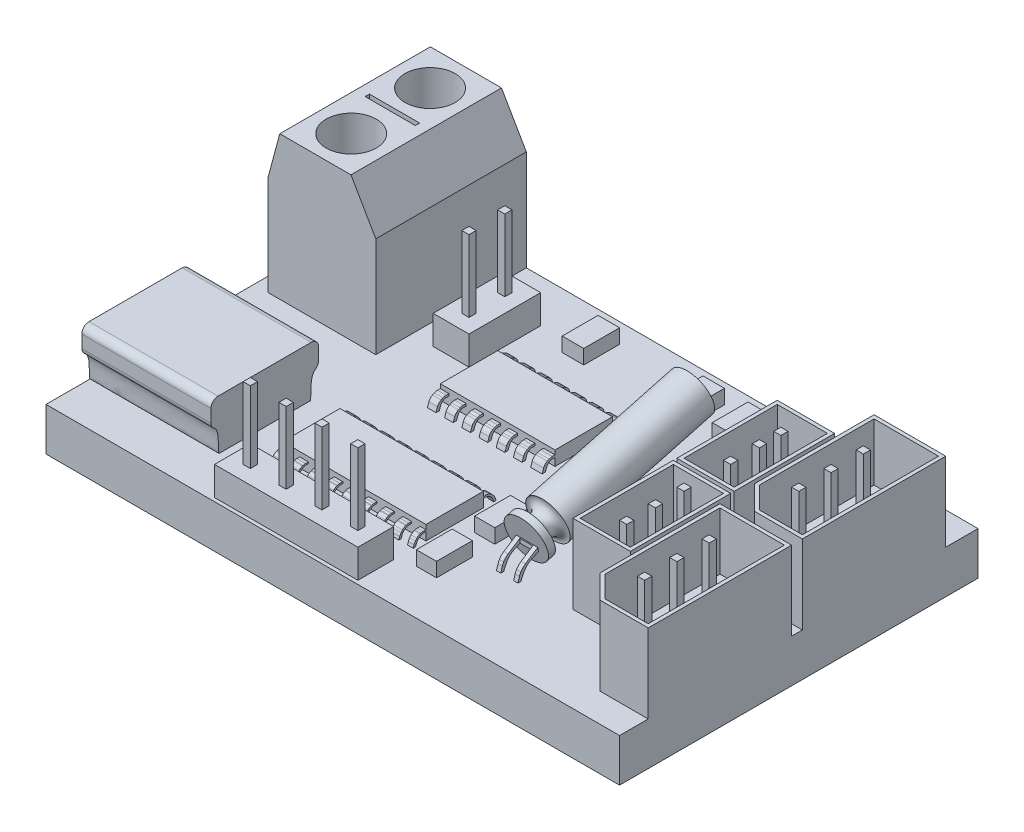
SolidWorks part; units mm, degrees
ref_plane "Front Plane" through (0, 0, 0) normal (0, 0, 1) x (1, 0, 0)
ref_plane "Top Plane" through (0, 0, 0) normal (0, 1, 0) x (1, 0, 0)
ref_plane "Right Plane" through (0, 0, 0) normal (1, 0, 0) x (0, 0, -1)
sketch "Sketch2" plane through (0, 0, 0) normal (0, 1, 0) x (1, 0, 0)
  line L1 (20, -12.5) -> (-20, -12.5)
  line L2 (20, -12.5) -> (20, 12.5)
  line L3 (20, 12.5) -> (-20, 12.5)
  line L4 (-20, -12.5) -> (-20, 12.5)
  line L5 (20, -12.5) -> (-20, 12.5) construction
  line L6 (20, 12.5) -> (-20, -12.5) construction
  point P0 (0, 0)
  dimension "D1" = 40
  dimension "D2" = 25
extrude "Boss-Extrude1" add sketch "Sketch2" against normal blind 3
sketch "Sketch3" plane through (0, 0, 0) normal (0, 1, 0) x (1, 0, 0)
  line L0 (20, 12.5) -> (-20, 12.5) construction
  line L1 (-19, 12.5) -> (-11.5, 12.5)
  line L2 (-19, 12.5) -> (-19, 2)
  line L3 (-19, 2) -> (-11.5, 2)
  line L4 (-11.5, 12.5) -> (-11.5, 2)
  line L5 (-20, 12.5) -> (-20, -12.5) construction
  dimension "D1" = 7.5
  dimension "D2" = 10.5
  dimension "D3" = 1
extrude "Boss-Extrude2" add sketch "Sketch3" along normal blind 10
sketch "Sketch4" plane through (0, 0, -2) normal (0, 0, 1) x (1, 0, 0)
  line L0 (-19, 7) -> (-18.1962, 10)
  line L1 (-19, 10) -> (-19, 0) construction
  line L2 (-19, 10) -> (-11.5, 10) construction
  line L3 (-18.1962, 10) -> (-19, 10)
  line L4 (-19, 10) -> (-19, 7)
  line L5 (-11.5, 7) -> (-13.2321, 10)
  line L6 (-11.5, 10) -> (-11.5, 0) construction
  line L7 (-13.2321, 10) -> (-11.5, 10)
  line L8 (-11.5, 10) -> (-11.5, 7)
  dimension "D1" = 3
  dimension "D2" = 3
  dimension "D3" = 15
  dimension "D4" = 30
extrude "Cut-Extrude1" cut sketch "Sketch4" against normal up to surface (10.5 mm away) up to face at (-7.625, 1.75, -12.5)
sketch "Sketch5" plane through (0, 10, 0) normal (0, 1, 0) x (1, 0, 0)
  line L0 (-13.2321, 12.5) -> (-18.1962, 12.5) construction
  line L1 (-17.4641, 7.522) -> (-13.9641, 7.522)
  line L2 (-17.4641, 7.522) -> (-17.4641, 7.222)
  line L3 (-17.4641, 7.222) -> (-13.9641, 7.222)
  line L4 (-13.9641, 7.522) -> (-13.9641, 7.222)
  line L5 (-19, 2) -> (-11.5, 2) construction
  circle A0 centre (-15.7141, 10) radius 1.75
  circle A1 centre (-15.7141, 4.5) radius 1.75
  point P10 (-15.7141, 12.5)
  point P11 (-15.7141, 7.522)
  dimension "D3" = 3.5
  dimension "D4" = 3.5
  dimension "D1" = 0.3
  dimension "D2" = 3.5
  dimension "D5" = 2.5
  dimension "D6" = 2.5
extrude "Cut-Extrude2" cut sketch "Sketch5" against normal blind 5
sketch "Sketch6" plane through (-19, 0, 0) normal (-1, 0, 0) x (0, 0, 1)
  line L0 (-2, 7) -> (-2, 0) construction
  line L1 (-12, 5.5) -> (-7.5, 5.5)
  line L2 (-12, 5.5) -> (-12, 1)
  line L3 (-12, 1) -> (-7.5, 1)
  line L4 (-7.5, 5.5) -> (-7.5, 1)
  line L5 (-12, 5.5) -> (-7.5, 1) construction
  line L6 (-12, 1) -> (-7.5, 5.5) construction
  line L7 (-7, 5.5) -> (-2.5, 5.5)
  line L8 (-7, 5.5) -> (-7, 1)
  line L9 (-7, 1) -> (-2.5, 1)
  line L10 (-2.5, 5.5) -> (-2.5, 1)
  line L11 (-7, 5.5) -> (-2.5, 1) construction
  line L12 (-7, 1) -> (-2.5, 5.5) construction
  line L13 (-12.5, 7) -> (-12.5, 0) construction
  line L14 (-12.5, 0) -> (-2, 0) construction
  point P0 (-9.75, 3.25)
  point P5 (-4.75, 3.25)
  point P10 (-10.0583, 3.2972)
  point P11 (-4.8741, 3.5631)
  point P12 (-10.0064, 3.0499)
  point P13 (-4.7649, 3.0499)
  point P14 (0, 0)
  point P15 (-10.1096, 3.1427)
  dimension "D1" = 4.5
  dimension "D2" = 4.5
  dimension "D3" = 4.5
  dimension "D4" = 4.5
  dimension "D5" = 0.5
  dimension "D6" = 0.5
  dimension "D7" = 1
extrude "Cut-Extrude3" cut sketch "Sketch6" against normal blind 5
sketch "Sketch7" plane through (0, 0, 0) normal (0, 1, 0) x (1, 0, 0)
  line L0 (-20, 12.5) -> (-20, -12.5) construction
  line L1 (-11, -10) -> (-20, -10)
  line L2 (-11, -10) -> (-11, -2.5)
  line L3 (-11, -2.5) -> (-20, -2.5)
  line L4 (-20, -10) -> (-20, -2.5)
  line L5 (-11, -10) -> (-20, -2.5) construction
  line L6 (-11, -2.5) -> (-20, -10) construction
  line L7 (-20, -12.5) -> (20, -12.5) construction
  point P0 (-15.5, -6.25)
  dimension "D1" = 7.5
  dimension "D2" = 9
  dimension "D3" = 2.5
extrude "Boss-Extrude3" add sketch "Sketch7" along normal blind 3.5
sketch "Sketch8" plane through (-20, 0, 0) normal (-1, 0, 0) x (0, 0, 1)
  line L0 (6.25, 5.2143) -> (6.25, -0.441) construction
  line L1 (2.5, 3.5) -> (10, 3.5) construction
  line L2 (2.5, 3.5) -> (2.5, 0) construction
  line L3 (2.5, 0) -> (3.1127, 0)
  line L4 (2.5, 1.75) -> (2.5, 0)
  line L5 (10, 1.75) -> (10, 0)
  line L6 (10, 0) -> (9.3873, 0)
  spline S0 degree 3 poles (2.5, 1.75) (3.2855, 1.8357) (2.8866, -0.1418) (3.1127, 0) knots 0 0 0 0 1 1 1 1
  spline S1 degree 3 poles (10, 1.75) (9.2145, 1.8357) (9.6134, -0.1418) (9.3873, 0) knots 0 0 0 0 1 1 1 1
  point P4 (6.25, 3.5)
  line M15 (10, 0) -> (10, 3.5)
  line M17 (2.5, 3.5) -> (2.5, 0)
extrude "Cut-Extrude4" cut sketch "Sketch8" against normal blind 13.5 contours S0 L3 M17 | S1 L6 M15 region at (-20, 0.8013, 2.7456) region at (-20, 0.8013, 9.7544)
fillet "Fillet1" radius 0.5 4 edges at (-15.5, 1.75, 10) (-15.5, 1.75, 2.5) (-15.5, 3.5, 2.5) (-15.5, 3.5, 10)
sketch "Sketch9" plane through (-20, 0, 0) normal (-1, 0, 0) x (0, 0, 1)
  line L0 (3.25, 0.25) -> (9.25, 0.25)
  line L1 (6.25, 3.8986) -> (6.25, 0.8013) construction
  line L2 (3, 3.5) -> (9.5, 3.5) construction
  line L3 (9.4263, 0) -> (12.5, 0) construction
  line L4 (9.4639, 3.25) -> (3.0361, 3.25)
  spline S0 degree 3 poles (9.25, 0.25) (9.2002, 0.8034) (9.2979, 1.1822) (9.4331, 1.8514) (9.7825, 1.9035) (9.8466, 2.3039) (9.7756, 2.7644) (9.8573, 3.2635) (9.4639, 3.25) knots 0 0 0 0 0.398944 0.460389 0.554943 0.650182 0.770421 1 1 1 1
  spline S1 degree 3 poles (3.25, 0.25) (3.2998, 0.8034) (3.2021, 1.1822) (3.0669, 1.8514) (2.7175, 1.9035) (2.6534, 2.3039) (2.7244, 2.7644) (2.6427, 3.2635) (3.0361, 3.25) knots 0 0 0 0 0.398944 0.460389 0.554943 0.650182 0.770421 1 1 1 1
  point P6 (6.25, 3.5)
  point P14 (6.25, 0.25)
  point P27 (6.25, 3.25)
  dimension "D1" = 3
  dimension "D2" = 0.25
  dimension "D3" = 0.25
extrude "Cut-Extrude5" cut sketch "Sketch9" against normal blind 8.5
sketch "Sketch10" plane through (0, 0, 0) normal (0, 1, 0) x (1, 0, 0)
  line L0 (-11.5, 2) -> (-11.5, 12.5) construction
  line L1 (-10, 9.5) -> (-7.5, 9.5)
  line L2 (-10, 9.5) -> (-10, 4.5)
  line L3 (-10, 4.5) -> (-7.5, 4.5)
  line L4 (-7.5, 9.5) -> (-7.5, 4.5)
  line L5 (-10, 9.5) -> (-7.5, 4.5) construction
  line L6 (-10, 4.5) -> (-7.5, 9.5) construction
  line L7 (20, 12.5) -> (-11.5, 12.5) construction
  point P0 (-8.75, 7)
  point P5 (-8.5445, 7.4217)
  dimension "D1" = 5
  dimension "D2" = 2.5
  dimension "D3" = 1.5
  dimension "D4" = 3
extrude "Boss-Extrude4" add sketch "Sketch10" along normal blind 2
sketch "Sketch11" plane through (0, 2, 0) normal (0, 1, 0) x (1, 0, 0)
  line L0 (-7.5, 9.5) -> (-10, 9.5) construction
  line L1 (-8.5, 8) -> (-9, 8)
  line L2 (-8.5, 8) -> (-8.5, 8.5)
  line L3 (-8.5, 8.5) -> (-9, 8.5)
  line L4 (-9, 8) -> (-9, 8.5)
  line L5 (-8.5, 8) -> (-9, 8.5) construction
  line L6 (-8.5, 8.5) -> (-9, 8) construction
  line L7 (-8.5027, 5.5) -> (-9.0027, 5.5)
  line L8 (-8.5027, 5.5) -> (-8.5027, 6)
  line L9 (-8.5027, 6) -> (-9.0027, 6)
  line L10 (-9.0027, 5.5) -> (-9.0027, 6)
  line L11 (-8.5027, 5.5) -> (-9.0027, 6) construction
  line L12 (-8.5027, 6) -> (-9.0027, 5.5) construction
  line L13 (-7.5, 4.5) -> (-7.5, 9.5) construction
  line L14 (-10, 4.5) -> (-7.5, 4.5) construction
  point P0 (-8.75, 8.25)
  point P5 (-8.7527, 5.75)
  dimension "D1" = 0.5
  dimension "D2" = 0.5
  dimension "D3" = 0.5
  dimension "D4" = 0.5
  dimension "D5" = 1.25
  dimension "D6" = 1.25
  dimension "D7" = 1.2527
  dimension "D8" = 1.25
extrude "Boss-Extrude5" add sketch "Sketch11" along normal blind 5
sketch "Sketch12" plane through (0, 0, 0) normal (0, 1, 0) x (1, 0, 0)
  line L0 (-11, -9.5) -> (-11, -3) construction
  line L1 (-8.5, -9.75) -> (1.5, -9.75)
  line L2 (-8.5, -9.75) -> (-8.5, -12.25)
  line L3 (-8.5, -12.25) -> (1.5, -12.25)
  line L4 (1.5, -9.75) -> (1.5, -12.25)
  line L5 (-20, -12.5) -> (20, -12.5) construction
  dimension "D1" = 2.5
  dimension "D2" = 10
  dimension "D3" = 2.5
  dimension "D4" = 0.25
extrude "Boss-Extrude6" add sketch "Sketch12" along normal blind 2
sketch "Sketch13" plane through (0, 2, 0) normal (0, 1, 0) x (1, 0, 0)
  line L0 (-8.5, -9.75) -> (-8.5, -12.25) construction
  line L1 (-7, -11.25) -> (-7.5, -11.25)
  line L2 (-7, -11.25) -> (-7, -10.75)
  line L3 (-7, -10.75) -> (-7.5, -10.75)
  line L4 (-7.5, -11.25) -> (-7.5, -10.75)
  line L5 (-7, -11.25) -> (-7.5, -10.75) construction
  line L6 (-7, -10.75) -> (-7.5, -11.25) construction
  line L8 (1.5, -9.75) -> (-8.5, -9.75) construction
  line L9 (-5, -11.25) -> (-5, -10.75)
  line L10 (-4.5, -10.75) -> (-5, -10.75)
  line L11 (-4.5, -11.25) -> (-4.5, -10.75)
  line L12 (-4.5, -11.25) -> (-5, -11.25)
  line L13 (-2.5, -11.25) -> (-2.5, -10.75)
  line L14 (-2, -10.75) -> (-2.5, -10.75)
  line L15 (-2, -11.25) -> (-2, -10.75)
  line L16 (-2, -11.25) -> (-2.5, -11.25)
  line L17 (0, -11.25) -> (0, -10.75)
  line L18 (0.5, -10.75) -> (0, -10.75)
  line L19 (0.5, -11.25) -> (0.5, -10.75)
  line L20 (0.5, -11.25) -> (0, -11.25)
  point P0 (-7.25, -11)
  dimension "D1" = 1.25
  dimension "D2" = 1.25
  dimension "D3" = 0.5
  dimension "D4" = 0.5
  dimension "D5" = 4
extrude "Boss-Extrude7" add sketch "Sketch13" along normal blind 5
sketch "Sketch14" plane through (0, 0, 0) normal (0, 1, 0) x (1, 0, 0)
  line L0 (-7.5, 4.5) -> (-7.5, 9.5) construction
  line L1 (-6.5, 5.5) -> (1.5, 5.5)
  line L2 (-6.5, 5.5) -> (-6.5, 1.5)
  line L3 (-6.5, 1.5) -> (1.5, 1.5)
  line L4 (1.5, 5.5) -> (1.5, 1.5)
  line L5 (-8.5, -3.5) -> (1.5, -3.5)
  line L6 (-8.5, -3.5) -> (-8.5, -7.5)
  line L7 (-8.5, -7.5) -> (1.5, -7.5)
  line L8 (1.5, -3.5) -> (1.5, -7.5)
  line L9 (20, 12.5) -> (-11.5, 12.5) construction
  dimension "D1" = 8
  dimension "D2" = 4
  dimension "D3" = 4
  dimension "D4" = 10
  dimension "D5" = 1
  dimension "D6" = 7
  dimension "D7" = 5
extrude "Boss-Extrude8" add sketch "Sketch14" along normal blind 1
sketch "Sketch15" plane through (1.5, 0, 0) normal (1, 0, 0) x (0, 0, -1)
  line L0 (1.5, 0.7025) -> (1.3027, 0.7025)
  line L1 (1.5, 1) -> (1.5, 0) construction
  line L2 (1.0838, 0.6521) -> (0.9577, 0.5907)
  line L3 (0.704, 0.3042) -> (0.599, 0)
  line L4 (-12.5, 0) -> (12.5, 0) construction
  line L5 (0.599, 0) -> (0.8295, 0)
  line L6 (0.8295, 0) -> (0.9119, 0.2391)
  line L7 (1.1657, 0.5256) -> (1.216, 0.5501)
  line L8 (1.216, 0.5501) -> (1.5, 0.5501)
  line L9 (3.5, 2.4985) -> (3.5, 0.0788) construction
  line L10 (1.5, 1) -> (5.5, 1) construction
  line L11 (1.5, 0.7025) -> (1.5, 0.5501)
  line L12 (5.5, 0.7025) -> (5.5, 0.5501)
  line L13 (5.784, 0.5501) -> (5.5, 0.5501)
  line L14 (5.8343, 0.5256) -> (5.784, 0.5501)
  line L15 (6.1705, 0) -> (6.0881, 0.2391)
  line L16 (6.401, 0) -> (6.1705, 0)
  line L17 (6.296, 0.3042) -> (6.401, 0)
  line L18 (5.9162, 0.6521) -> (6.0423, 0.5907)
  line L19 (5.5, 0.7025) -> (5.6973, 0.7025)
  arc A0 (1.3027, 0.7025) -> (1.0838, 0.6521) centre (1.3027, 0.2025) ccw
  arc A1 (0.9119, 0.2391) -> (1.1657, 0.5256) centre (1.3846, 0.076) cw
  arc A2 (0.704, 0.3042) -> (0.9577, 0.5907) centre (1.1767, 0.1412) cw
  arc A3 (6.296, 0.3042) -> (6.0423, 0.5907) centre (5.8233, 0.1412) ccw
  arc A4 (6.0881, 0.2391) -> (5.8343, 0.5256) centre (5.6154, 0.076) ccw
  arc A5 (5.6973, 0.7025) -> (5.9162, 0.6521) centre (5.6973, 0.2025) cw
  point P16 (3.5, 1)
  dimension "D1" = 0.5
extrude "Boss-Extrude9" add sketch "Sketch15" against normal up to surface (8 mm away) up to face at (-6.5, 0.5, -3.5)
sketch "Sketch16" plane through (1.5, 0, 0) normal (1, 0, 0) x (0, 0, -1)
  line L0 (-7.5, 0.6782) -> (-7.7045, 0.6782)
  line L1 (-7.5, 1) -> (-7.5, 0) construction
  line L2 (-7.8691, 0.6503) -> (-7.9154, 0.6342)
  line L3 (-8.1339, 0.4833) -> (-8.2332, 0.3648)
  line L4 (-8.3282, 0.1901) -> (-8.3864, 0)
  line L5 (-12.5, 0) -> (12.5, 0) construction
  line L6 (-8.3864, 0) -> (-8.2252, 0)
  line L7 (-8.2252, 0) -> (-8.1768, 0.1579)
  line L8 (-8.0819, 0.3327) -> (-8.0568, 0.3626)
  line L9 (-7.9199, 0.4766) -> (-7.8668, 0.5066)
  line L10 (-7.6206, 0.5714) -> (-7.5, 0.5714)
  line L11 (-7.5, 0.6782) -> (-7.5, 0.5714)
  line L12 (-5.5, 2.2485) -> (-5.5, -1.2373) construction
  line L13 (-7.5, 1) -> (-3.5, 1) construction
  line L14 (-3.5, 0.6782) -> (-3.5, 0.5714)
  line L15 (-3.3794, 0.5714) -> (-3.5, 0.5714)
  line L16 (-3.0801, 0.4766) -> (-3.1332, 0.5066)
  line L17 (-2.9181, 0.3327) -> (-2.9432, 0.3626)
  line L18 (-2.7748, 0) -> (-2.8232, 0.1579)
  line L19 (-2.6136, 0) -> (-2.7748, 0)
  line L20 (-2.6718, 0.1901) -> (-2.6136, 0)
  line L21 (-2.8661, 0.4833) -> (-2.7668, 0.3648)
  line L22 (-3.1309, 0.6503) -> (-3.0846, 0.6342)
  line L23 (-3.5, 0.6782) -> (-3.2955, 0.6782)
  arc A1 (-7.7045, 0.6782) -> (-7.8691, 0.6503) centre (-7.7045, 0.1782) ccw
  arc A2 (-7.8668, 0.5066) -> (-7.6206, 0.5714) centre (-7.6206, 0.0714) cw
  arc A3 (-8.0568, 0.3626) -> (-7.9199, 0.4766) centre (-7.6737, 0.0414) cw
  arc A4 (-8.1768, 0.1579) -> (-8.0819, 0.3327) centre (-7.6987, 0.0115) cw
  arc A5 (-8.2332, 0.3648) -> (-8.3282, 0.1901) centre (-7.8501, 0.0436) ccw
  arc A6 (-7.9154, 0.6342) -> (-8.1339, 0.4833) centre (-7.7508, 0.1621) ccw
  arc A7 (-3.0846, 0.6342) -> (-2.8661, 0.4833) centre (-3.2492, 0.1621) cw
  arc A8 (-2.7668, 0.3648) -> (-2.6718, 0.1901) centre (-3.1499, 0.0436) cw
  arc A9 (-2.8232, 0.1579) -> (-2.9181, 0.3327) centre (-3.3013, 0.0115) ccw
  arc A10 (-2.9432, 0.3626) -> (-3.0801, 0.4766) centre (-3.3263, 0.0414) ccw
  arc A11 (-3.1332, 0.5066) -> (-3.3794, 0.5714) centre (-3.3794, 0.0714) ccw
  arc A12 (-3.2955, 0.6782) -> (-3.1309, 0.6503) centre (-3.2955, 0.1782) cw
  point P16 (-5.5, 1)
  dimension "D1" = 0.5
extrude "Boss-Extrude10" add sketch "Sketch16" against normal up to surface (10 mm away) up to face at (-8.5, 0.5, 5.5)
sketch "Sketch17" plane through (0, 0, 0) normal (0, 1, 0) x (1, 0, 0)
  line L0 (-6.5, 6.401) -> (1.5, 6.401) construction
  line L1 (-5.9, 6.401) -> (-5.3, 6.401)
  line L2 (-5.9, 6.401) -> (-5.9, 5.5)
  line L3 (-5.9, 5.5) -> (-5.3, 5.5)
  line L4 (-5.3, 6.401) -> (-5.3, 5.5)
  line L5 (-6.5, 5.5) -> (1.5, 5.5) construction
  line L6 (-6.5, 1.5) -> (1.5, 1.5) construction
  line L7 (-5.9, 1.5) -> (-5.3, 1.5)
  line L8 (-5.9, 1.5) -> (-5.9, 0.599)
  line L9 (-5.9, 0.599) -> (-5.3, 0.599)
  line L10 (-5.3, 1.5) -> (-5.3, 0.599)
  line L11 (-6.5, 0.599) -> (1.5, 0.599) construction
  line L12 (-6.5, 6.296) -> (-6.5, 6.0423) construction
  line L13 (-4.1, 1.5) -> (-4.1, 0.599)
  line L14 (-4.7, 1.5) -> (-4.1, 1.5)
  line L15 (-4.7, 1.5) -> (-4.7, 0.599)
  line L16 (-4.7, 0.599) -> (-4.1, 0.599)
  line L17 (-4.7, 5.5) -> (-4.1, 5.5)
  line L18 (-4.7, 6.401) -> (-4.7, 5.5)
  line L19 (-4.1, 6.401) -> (-4.1, 5.5)
  line L20 (-4.7, 6.401) -> (-4.1, 6.401)
  line L21 (-2.9, 1.5) -> (-2.9, 0.599)
  line L22 (-3.5, 1.5) -> (-2.9, 1.5)
  line L23 (-3.5, 1.5) -> (-3.5, 0.599)
  line L24 (-3.5, 0.599) -> (-2.9, 0.599)
  line L25 (-3.5, 5.5) -> (-2.9, 5.5)
  line L26 (-3.5, 6.401) -> (-3.5, 5.5)
  line L27 (-2.9, 6.401) -> (-2.9, 5.5)
  line L28 (-3.5, 6.401) -> (-2.9, 6.401)
  line L29 (-1.7, 1.5) -> (-1.7, 0.599)
  line L30 (-2.3, 1.5) -> (-1.7, 1.5)
  line L31 (-2.3, 1.5) -> (-2.3, 0.599)
  line L32 (-2.3, 0.599) -> (-1.7, 0.599)
  line L33 (-2.3, 5.5) -> (-1.7, 5.5)
  line L34 (-2.3, 6.401) -> (-2.3, 5.5)
  line L35 (-1.7, 6.401) -> (-1.7, 5.5)
  line L36 (-2.3, 6.401) -> (-1.7, 6.401)
  line L37 (-0.5, 1.5) -> (-0.5, 0.599)
  line L38 (-1.1, 1.5) -> (-0.5, 1.5)
  line L39 (-1.1, 1.5) -> (-1.1, 0.599)
  line L40 (-1.1, 0.599) -> (-0.5, 0.599)
  line L41 (-1.1, 5.5) -> (-0.5, 5.5)
  line L42 (-1.1, 6.401) -> (-1.1, 5.5)
  line L43 (-0.5, 6.401) -> (-0.5, 5.5)
  line L44 (-1.1, 6.401) -> (-0.5, 6.401)
  line L45 (0.7, 1.5) -> (0.7, 0.599)
  line L46 (0.1, 1.5) -> (0.7, 1.5)
  line L47 (0.1, 1.5) -> (0.1, 0.599)
  line L48 (0.1, 0.599) -> (0.7, 0.599)
  line L49 (0.1, 5.5) -> (0.7, 5.5)
  line L50 (0.1, 6.401) -> (0.1, 5.5)
  line L51 (0.7, 6.401) -> (0.7, 5.5)
  line L52 (0.1, 6.401) -> (0.7, 6.401)
  line L53 (-8.5, -2.6136) -> (1.5, -2.6136) construction
  line L54 (-7.9, -2.6136) -> (-7.3, -2.6136)
  line L55 (-7.9, -2.6136) -> (-7.9, -3.5)
  line L56 (-7.9, -3.5) -> (-7.3, -3.5)
  line L57 (-7.3, -2.6136) -> (-7.3, -3.5)
  line L58 (1.5, -3.5) -> (-8.5, -3.5) construction
  line L59 (-8.5, -7.5) -> (1.5, -7.5) construction
  line L60 (-7.9, -7.5) -> (-7.3, -7.5)
  line L61 (-7.9, -7.5) -> (-7.9, -8.3864)
  line L62 (-7.9, -8.3864) -> (-7.3, -8.3864)
  line L63 (-7.3, -7.5) -> (-7.3, -8.3864)
  line L64 (-8.5, -8.3864) -> (1.5, -8.3864) construction
  line L65 (-8.5, -2.8661) -> (-8.5, -3.0846) construction
  line L66 (-8.5, -7.7045) -> (-8.5, -7.8691) construction
  line L67 (-6.7, -2.6136) -> (-6.7, -3.5)
  line L68 (-6.7, -2.6136) -> (-6.1, -2.6136)
  line L69 (-6.1, -2.6136) -> (-6.1, -3.5)
  line L70 (-6.7, -3.5) -> (-6.1, -3.5)
  line L71 (-6.7, -7.5) -> (-6.7, -8.3864)
  line L72 (-6.7, -7.5) -> (-6.1, -7.5)
  line L73 (-6.1, -7.5) -> (-6.1, -8.3864)
  line L74 (-6.7, -8.3864) -> (-6.1, -8.3864)
  line L75 (-5.5, -2.6136) -> (-5.5, -3.5)
  line L76 (-5.5, -2.6136) -> (-4.9, -2.6136)
  line L77 (-4.9, -2.6136) -> (-4.9, -3.5)
  line L78 (-5.5, -3.5) -> (-4.9, -3.5)
  line L79 (-5.5, -7.5) -> (-5.5, -8.3864)
  line L80 (-5.5, -7.5) -> (-4.9, -7.5)
  line L81 (-4.9, -7.5) -> (-4.9, -8.3864)
  line L82 (-5.5, -8.3864) -> (-4.9, -8.3864)
  line L83 (-4.3, -2.6136) -> (-4.3, -3.5)
  line L84 (-4.3, -2.6136) -> (-3.7, -2.6136)
  line L85 (-3.7, -2.6136) -> (-3.7, -3.5)
  line L86 (-4.3, -3.5) -> (-3.7, -3.5)
  line L87 (-4.3, -7.5) -> (-4.3, -8.3864)
  line L88 (-4.3, -7.5) -> (-3.7, -7.5)
  line L89 (-3.7, -7.5) -> (-3.7, -8.3864)
  line L90 (-4.3, -8.3864) -> (-3.7, -8.3864)
  line L91 (-3.1, -2.6136) -> (-3.1, -3.5)
  line L92 (-3.1, -2.6136) -> (-2.5, -2.6136)
  line L93 (-2.5, -2.6136) -> (-2.5, -3.5)
  line L94 (-3.1, -3.5) -> (-2.5, -3.5)
  line L95 (-3.1, -7.5) -> (-3.1, -8.3864)
  line L96 (-3.1, -7.5) -> (-2.5, -7.5)
  line L97 (-2.5, -7.5) -> (-2.5, -8.3864)
  line L98 (-3.1, -8.3864) -> (-2.5, -8.3864)
  line L99 (-1.9, -2.6136) -> (-1.9, -3.5)
  line L100 (-1.9, -2.6136) -> (-1.3, -2.6136)
  line L101 (-1.3, -2.6136) -> (-1.3, -3.5)
  line L102 (-1.9, -3.5) -> (-1.3, -3.5)
  line L103 (-1.9, -7.5) -> (-1.9, -8.3864)
  line L104 (-1.9, -7.5) -> (-1.3, -7.5)
  line L105 (-1.3, -7.5) -> (-1.3, -8.3864)
  line L106 (-1.9, -8.3864) -> (-1.3, -8.3864)
  line L107 (-0.7, -2.6136) -> (-0.7, -3.5)
  line L108 (-0.7, -2.6136) -> (-0.1, -2.6136)
  line L109 (-0.1, -2.6136) -> (-0.1, -3.5)
  line L110 (-0.7, -3.5) -> (-0.1, -3.5)
  line L111 (-0.7, -7.5) -> (-0.7, -8.3864)
  line L112 (-0.7, -7.5) -> (-0.1, -7.5)
  line L113 (-0.1, -7.5) -> (-0.1, -8.3864)
  line L114 (-0.7, -8.3864) -> (-0.1, -8.3864)
  line L115 (0.5, -2.6136) -> (0.5, -3.5)
  line L116 (0.5, -2.6136) -> (1.1, -2.6136)
  line L117 (1.1, -2.6136) -> (1.1, -3.5)
  line L118 (0.5, -3.5) -> (1.1, -3.5)
  line L119 (0.5, -7.5) -> (0.5, -8.3864)
  line L120 (0.5, -7.5) -> (1.1, -7.5)
  line L121 (1.1, -7.5) -> (1.1, -8.3864)
  line L122 (0.5, -8.3864) -> (1.1, -8.3864)
  dimension "D1" = 0.6
  dimension "D2" = 0.6
  dimension "D3" = 0.6
  dimension "D5" = 0.6
  dimension "D6" = 0.6
  dimension "D7" = 0.6
  dimension "D8" = 0.6
  dimension "D4" = 6
  dimension "D9" = 8
extrude "Cut-Extrude6" cut sketch "Sketch17" along normal blind 1
sketch "Sketch18" plane through (0, 0, 0) normal (0, 1, 0) x (1, 0, 0)
  line L0 (15.25, 10) -> (19.75, 10)
  line L1 (19.75, 10) -> (19.75, 0.5)
  line L2 (19.75, 0.5) -> (16.75, 0.5)
  line L5 (16.75, 0.5) -> (15.25, 2)
  line L6 (15.25, 2) -> (15.25, 10)
  line L7 (20, -12.5) -> (20, 12.5) construction
  line L8 (20, 12.5) -> (-11.5, 12.5) construction
  line L9 (15.25, -0.75) -> (19.75, -0.75)
  line L10 (19.75, -0.75) -> (19.75, -10.25)
  line L11 (19.75, -10.25) -> (16.75, -10.25)
  line L12 (16.75, -10.25) -> (15.25, -8.75)
  line L13 (15.25, -8.75) -> (15.25, -0.75)
  line L14 (-20, -12.5) -> (20, -12.5) construction
  line L21 (11, 7.5) -> (14.5, 7.5)
  line L22 (11, 7.5) -> (11, 1)
  line L23 (11, 1) -> (14.5, 1)
  line L24 (14.5, 7.5) -> (14.5, 1)
  line L25 (11, 0.25) -> (14.5, 0.25)
  line L26 (11, 0.25) -> (11, -6.25)
  line L27 (11, -6.25) -> (14.5, -6.25)
  line L28 (14.5, 0.25) -> (14.5, -6.25)
  dimension "D1" = 9.5
  dimension "D2" = 4.5
  dimension "D3" = 135
  dimension "D4" = 0.25
  dimension "D5" = 2.5
  dimension "D6" = 3
  dimension "D7" = 135
  dimension "D8" = 3
  dimension "D9" = 9.5
  dimension "D10" = 4.5
  dimension "D11" = 0.25
  dimension "D12" = 2.25
  dimension "D13" = 3.5
  dimension "D14" = 3.5
  dimension "D15" = 6.5
  dimension "D16" = 6.5
  dimension "D17" = 0.75
  dimension "D18" = 0.75
  dimension "D19" = 2.5
  dimension "D20" = 0.75
extrude "Extrude-Thin1" add sketch "Sketch18" along normal blind 5.5 thin thin type one direction wall 0.25
sketch "Sketch19" plane through (0, 0, 0) normal (0, 1, 0) x (1, 0, 0)
  line L0 (19.75, 0.5) -> (19.75, 10) construction
  line L1 (11, 7.5) -> (14.5, 7.5)
  line L2 (11, 7.5) -> (11, 1)
  line L3 (11, 1) -> (14.5, 1)
  line L4 (14.5, 7.5) -> (14.5, 1)
  line L5 (11, 0.25) -> (14.5, 0.25)
  line L6 (11, 0.25) -> (11, -6.25)
  line L7 (11, -6.25) -> (14.5, -6.25)
  line L8 (14.5, 0.25) -> (14.5, -6.25)
  line L9 (19.75, 10) -> (15.25, 10) construction
  line L10 (15.25, 10) -> (15.25, 2) construction
  line L11 (15.25, 2) -> (16.75, 0.5) construction
  line L12 (16.75, 0.5) -> (19.75, 0.5) construction
  line L13 (19.75, -10.25) -> (19.75, -0.75) construction
  line L14 (19.75, -0.75) -> (15.25, -0.75) construction
  line L15 (15.25, -0.75) -> (15.25, -8.75) construction
  line L16 (15.25, -8.75) -> (16.75, -10.25) construction
  line L17 (16.75, -10.25) -> (19.75, -10.25) construction
  line L18 (19.75, 0.5) -> (19.75, 10)
  line L19 (19.75, 10) -> (15.25, 10)
  line L20 (15.25, 10) -> (15.25, 2)
  line L21 (15.25, 2) -> (16.75, 0.5)
  line L22 (16.75, 0.5) -> (19.75, 0.5)
  line L23 (19.75, -10.25) -> (19.75, -0.75)
  line L24 (19.75, -0.75) -> (15.25, -0.75)
  line L25 (15.25, -0.75) -> (15.25, -8.75)
  line L26 (15.25, -8.75) -> (16.75, -10.25)
  line L27 (16.75, -10.25) -> (19.75, -10.25)
extrude "Boss-Extrude11" add sketch "Sketch19" along normal blind 1.5
sketch "Sketch20" plane through (0, 1.5, 0) normal (0, 1, 0) x (1, 0, 0)
  line L0 (16.5, 5.25) -> (17, 5.25)
  line L1 (16.5, 8) -> (17, 8)
  line L2 (16.5, 8) -> (16.5, 7.5)
  line L3 (16.5, 7.5) -> (17, 7.5)
  line L4 (17, 8) -> (17, 7.5)
  line L5 (16.5, 5.25) -> (16.5, 5.75)
  line L6 (16.5, 5.75) -> (17, 5.75)
  line L7 (17, 5.25) -> (17, 5.75)
  line L8 (16.5, 3.5) -> (17, 3.5)
  line L9 (16.5, 3.5) -> (16.5, 3)
  line L10 (16.5, 3) -> (17, 3)
  line L11 (17, 3.5) -> (17, 3)
  line L12 (16.5, -2.75) -> (17, -2.75)
  line L13 (16.5, -2.75) -> (16.5, -3.25)
  line L14 (16.5, -3.25) -> (17, -3.25)
  line L15 (17, -2.75) -> (17, -3.25)
  line L16 (16.5, -5) -> (17, -5)
  line L17 (16.5, -5) -> (16.5, -5.5)
  line L18 (16.5, -5.5) -> (17, -5.5)
  line L19 (17, -5) -> (17, -5.5)
  line L20 (16.5, -7.25) -> (17, -7.25)
  line L21 (16.5, -7.25) -> (16.5, -7.75)
  line L22 (16.5, -7.75) -> (17, -7.75)
  line L23 (17, -7.25) -> (17, -7.75)
  line L24 (12.5, -0.5) -> (13, -0.5)
  line L25 (12.5, -0.5) -> (12.5, -1)
  line L26 (12.5, -1) -> (13, -1)
  line L27 (13, -0.5) -> (13, -1)
  line L28 (12.5, -2.5) -> (13, -2.5)
  line L29 (12.5, -2.5) -> (12.5, -3)
  line L30 (12.5, -3) -> (13, -3)
  line L31 (13, -2.5) -> (13, -3)
  line L32 (12.5, -4.5) -> (13, -4.5)
  line L33 (12.5, -4.5) -> (12.5, -5)
  line L34 (12.5, -5) -> (13, -5)
  line L35 (13, -4.5) -> (13, -5)
  line L36 (12.5, 2.75) -> (13, 2.75)
  line L37 (12.5, 2.75) -> (12.5, 2.25)
  line L38 (12.5, 2.25) -> (13, 2.25)
  line L39 (13, 2.75) -> (13, 2.25)
  line L40 (12.5, 4.75) -> (13, 4.75)
  line L41 (12.5, 4.75) -> (12.5, 4.25)
  line L42 (12.5, 4.25) -> (13, 4.25)
  line L43 (13, 4.75) -> (13, 4.25)
  line L44 (12.5, 5.75) -> (13, 5.75)
  line L45 (12.5, 5.75) -> (12.5, 6.25)
  line L46 (12.5, 6.25) -> (13, 6.25)
  line L47 (13, 5.75) -> (13, 6.25)
  line L48 (11, 1) -> (14.5, 1) construction
  line L49 (11, 7.5) -> (11, 1) construction
  line L51 (11, -6.25) -> (14.5, -6.25) construction
  line L52 (19.75, 10) -> (15.25, 10) construction
  line L53 (15.25, 10) -> (15.25, 2) construction
  line L55 (19.75, -0.75) -> (15.25, -0.75) construction
  point P52 (12.9792, 2.5)
  point P55 (16.9559, 5.5099)
  dimension "D1" = 0.5
  dimension "D2" = 0.5
  dimension "D3" = 1.5
  dimension "D4" = 1.5
  dimension "D5" = 1.25
  dimension "D6" = 1.5
  dimension "D7" = 0.5
  dimension "D8" = 0.5
  dimension "D9" = 0.5
  dimension "D10" = 0.5
  dimension "D11" = 0.5
  dimension "D12" = 0.5
  dimension "D13" = 0.5
  dimension "D14" = 0.5
  dimension "D15" = 0.5
  dimension "D16" = 0.5
  dimension "D17" = 1.25
  dimension "D18" = 1.5
  dimension "D19" = 1.5
  dimension "D20" = 0.5
  dimension "D21" = 0.5
  dimension "D22" = 1.75
  dimension "D23" = 1.75
  dimension "D24" = 2
  dimension "D25" = 1.25
  dimension "D26" = 1.75
  dimension "D27" = 1.75
  dimension "D28" = 0.5
  dimension "D29" = 0.5
  dimension "D30" = 0.5
  dimension "D31" = 0.5
  dimension "D32" = 2
extrude "Boss-Extrude12" add sketch "Sketch20" along normal up to surface (4 mm away) up to face at (12.75, 5.5, -4.25)
ref_plane "Plane1" through (6.5, 0, 0) normal (1, 0, 0) x (0, 0, -1)
sketch "Sketch21" plane through (6.5, 0, 0) normal (1, 0, 0) x (0, 0, -1)
  line L0 (-8.8936, 0.7228) -> (16.1457, 7.4321) construction
  line L1 (-2.6456, 0) -> (5.105, 0) construction
  line L2 (-5.5, 1.6321) -> (-5.1118, 0.1832)
  line L3 (-3.6099, 0.5856) -> (6.4793, 3.289)
  line L4 (6.4793, 3.289) -> (6.0911, 4.7379)
  line L5 (-5.1118, 0.1832) -> (-4.6288, 0.3126)
  line L6 (-5.5, 1.6321) -> (6.0911, 4.7379)
  arc A0 (-3.6099, 0.5856) -> (-4.6288, 0.3126) centre (-4.1597, 0.5998) ccw
  dimension "D3" = 0.55
  dimension "D1" = 15
  dimension "D2" = 3
  dimension "D4" = 1.5
  dimension "D5" = 12
  dimension "D6" = 0.5
  dimension "D7" = 5.5
revolve "Revolve1" add sketch "Sketch21" angle 360 about L0
sketch "Sketch22" plane through (6.5, 0, 0) normal (1, 0, 0) x (0, 0, -1)
  line L0 (-0.2315, 0) -> (-9.1302, 0) construction
  line L1 (-5.3855, 1.2048) -> (-5.9749, 0.9066)
  line L2 (-5.8882, 3.081) -> (-5.1118, 0.1832) construction
  line L3 (-6.3822, 0.5266) -> (-6.4098, 0.4803)
  line L4 (-6.4684, 0.3662) -> (-6.6273, 0)
  line L5 (-6.6273, 0) -> (-6.8363, 0)
  line L6 (-6.8363, 0) -> (-6.7304, 0.3506)
  line L7 (-6.632, 0.5737) -> (-6.6309, 0.5755)
  line L8 (-6.3158, 0.9024) -> (-5.4541, 1.4608)
  line L9 (-5.4541, 1.4608) -> (-5.3855, 1.2048)
  arc A0 (-5.9749, 0.9066) -> (-6.3822, 0.5266) centre (-5.5234, 0.0143) ccw
  arc A1 (-6.4098, 0.4803) -> (-6.4684, 0.3662) centre (-5.551, -0.0319) ccw
  arc A2 (-6.7304, 0.3506) -> (-6.632, 0.5737) centre (-5.7732, 0.0614) cw
  arc A3 (-6.6309, 0.5755) -> (-6.3158, 0.9024) centre (-5.7721, 0.0632) cw
  dimension "D1" = 1
extrude "Boss-Extrude13" add sketch "Sketch22" along normal mid plane 1.5
sketch "Sketch24" plane through (0, 0, 12.5) normal (0, 0, 1) x (1, 0, 0)
  line L0 (7.25, 1.4608) -> (5.75, 1.4608) construction
  line L1 (6.05, 1.4608) -> (6.95, 1.4608)
  line L2 (6.05, 1.4608) -> (6.05, 0)
  line L3 (6.05, 0) -> (6.95, 0)
  line L4 (6.95, 1.4608) -> (6.95, 0)
  line L5 (-20, 0) -> (20, 0) construction
  line L6 (5.75, 1.4608) -> (5.75, 0.9024) construction
  line L7 (7.25, 1.4608) -> (7.25, 0.9024) construction
  dimension "D1" = 0.3
  dimension "D2" = 0.3
extrude "Cut-Extrude7" cut sketch "Sketch24" against normal blind 7
sketch "Sketch25" plane through (0, 0, 0) normal (0, 1, 0) x (1, 0, 0)
  line L0 (3.6854, 8.6309) -> (2.1854, 8.6309)
  line L1 (-3.6277, 8.6309) -> (-5.1277, 8.6309)
  line L2 (-3.6277, 8.6309) -> (-3.6277, 11.1309)
  line L3 (-3.6277, 11.1309) -> (-5.1277, 11.1309)
  line L4 (-5.1277, 8.6309) -> (-5.1277, 11.1309)
  line L5 (-3.6277, 8.6309) -> (-5.1277, 11.1309) construction
  line L6 (-3.6277, 11.1309) -> (-5.1277, 8.6309) construction
  line L7 (3.6854, 8.6309) -> (3.6854, 11.1309)
  line L8 (3.6854, 11.1309) -> (2.1854, 11.1309)
  line L9 (2.1854, 8.6309) -> (2.1854, 11.1309)
  line L10 (3.6854, 8.6309) -> (2.1854, 11.1309) construction
  line L11 (3.6854, 11.1309) -> (2.1854, 8.6309) construction
  line L12 (6.8331, 8.6309) -> (5.3331, 8.6309)
  line L13 (6.8331, 8.6309) -> (6.8331, 11.1309)
  line L14 (6.8331, 11.1309) -> (5.3331, 11.1309)
  line L15 (5.3331, 8.6309) -> (5.3331, 11.1309)
  line L16 (6.8331, 8.6309) -> (5.3331, 11.1309) construction
  line L17 (6.8331, 11.1309) -> (5.3331, 8.6309) construction
  line L18 (9.6668, 8.6309) -> (8.1668, 8.6309)
  line L19 (9.6668, 8.6309) -> (9.6668, 11.1309)
  line L20 (9.6668, 11.1309) -> (8.1668, 11.1309)
  line L21 (8.1668, 8.6309) -> (8.1668, 11.1309)
  line L22 (9.6668, 8.6309) -> (8.1668, 11.1309) construction
  line L23 (9.6668, 11.1309) -> (8.1668, 8.6309) construction
  line L24 (4.0958, -5.2967) -> (2.6919, -5.2967)
  line L25 (4.0958, -5.2967) -> (4.0958, -2.7967)
  line L26 (4.0958, -2.7967) -> (2.6919, -2.7967)
  line L27 (2.6919, -5.2967) -> (2.6919, -2.7967)
  line L28 (4.0958, -5.2967) -> (2.6919, -2.7967) construction
  line L29 (4.0958, -2.7967) -> (2.6919, -5.2967) construction
  line L30 (4.0958, -9.3613) -> (2.6919, -9.3613)
  line L31 (4.0958, -9.3613) -> (4.0958, -6.8613)
  line L32 (4.0958, -6.8613) -> (2.6919, -6.8613)
  line L33 (2.6919, -9.3613) -> (2.6919, -6.8613)
  line L34 (4.0958, -9.3613) -> (2.6919, -6.8613) construction
  line L35 (4.0958, -6.8613) -> (2.6919, -9.3613) construction
  point P0 (-4.3777, 9.8809)
  point P5 (-4.3777, 9.9563)
  point P6 (2.9354, 9.8809)
  point P11 (6.0831, 9.8809)
  point P16 (8.9168, 9.8809)
  point P21 (6.0831, 9.8244)
  point P22 (2.9354, 9.8809)
  point P23 (3.3938, -4.0467)
  point P28 (3.3938, -8.1113)
  point P33 (3.0755, -4.3731)
  point P34 (3.1031, -4.491)
  point P35 (3.3938, -4.0467)
  dimension "D1" = 1.5
  dimension "D2" = 2.5
  dimension "D3" = 2.5
  dimension "D4" = 2.5
  dimension "D5" = 2.5
  dimension "D6" = 2.5
  dimension "D7" = 2.5
extrude "Boss-Extrude14" add sketch "Sketch25" along normal blind 1
ref_plane "Plane2" through (0, -3, 0) normal (0, 1, 0) x (1, 0, 0)
sketch "Sketch26" plane through (0, -3, 0) normal (0, 1, 0) x (1, 0, 0)
  line L0 (-20, 12.5) -> (-20, -12.5) construction
  line L1 (20, 12.5) -> (-20, 12.5)
  line L2 (20, 12.5) -> (20, -12.5)
  line L3 (20, -12.5) -> (-20, -12.5)
  line L4 (-20, 12.5) -> (-20, -12.5)
  line L5 (20, 12.5) -> (-20, -12.5) construction
  line L6 (20, -12.5) -> (-20, 12.5) construction
  line L7 (-20, -9.4263) -> (-20, -12.5) construction
  point P0 (0, 0)
  dimension "D1" = 25
extrude "Boss-Extrude15" add sketch "Sketch26" along normal blind 3
